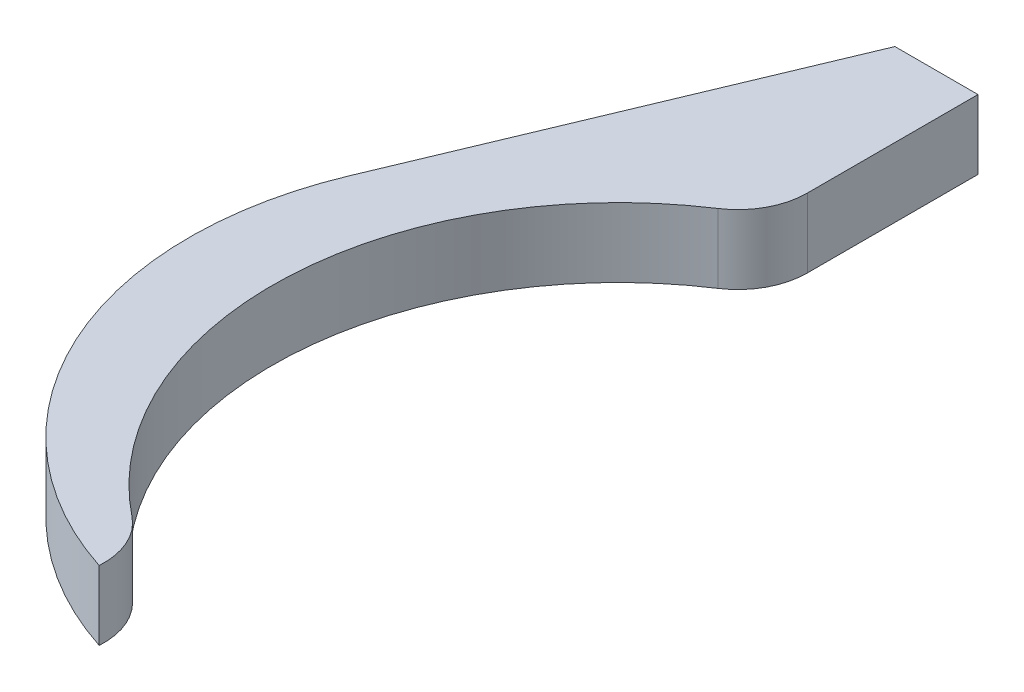
SolidWorks part; units mm, degrees
ref_plane "前视基准面" through (0, 0, 0) normal (0, 0, 1) x (1, 0, 0)
ref_plane "上视基准面" through (0, 0, 0) normal (0, 1, 0) x (1, 0, 0)
ref_plane "右视基准面" through (0, 0, 0) normal (1, 0, 0) x (0, 0, -1)
other "Configuration Table"
sketch "草图3" plane through (0, 0, 0) normal (0, 1, 0) x (1, 0, 0)
  line L0 (0, 0) -> (0, -9.9636) construction
  line L1 (-3, -3.3541) -> (3, -3.3541) construction
  line L2 (-3, -3.3541) -> (-3, -7.4162)
  line L3 (3, -3.3541) -> (3, -7.4162)
  line L7 (3, -7.4162) -> (3, -10.583)
  line L10 (-3, -43.8541) -> (3, -43.8541)
  line L11 (3, -43.8541) -> (3, -10.583)
  line L13 (-3, -7.4162) -> (-3, -43.8541)
  arc A0 (3, -3.3541) -> (-3, -3.3541) centre (0, 0) ccw
  point P6 (0, -3.3541)
  dimension "D1" = 9
  dimension "D2" = 6
  dimension "16.66" = 40.5
extrude "凸台-拉伸2" add sketch "草图3" along normal blind 5
sketch "草图4" plane through (0, 5, 0) normal (0, 1, 0) x (1, 0, 0)
  circle A0 centre (0, 0) radius 1.65
  dimension "D1" = 3.3
extrude "切除-拉伸1" cut sketch "草图4" against normal up to surface (5 mm away) up to face at (0, 0, 21.6406)
sketch "草图6" plane through (0, 5, 0) normal (0, 1, 0) x (1, 0, 0)
  line L0 (14.4495, -55.9701) -> (14.4495, -20.0301) construction
  line L1 (14.4495, -55.9701) -> (3, -43.8541) construction
  line L2 (3, -68.0861) -> (0.6636, -72.1328) construction
  line L3 (3, -43.8541) -> (-3, -43.8541) construction
  line L4 (3, -43.8541) -> (3, -33.746) construction
  line L5 (3, -43.8541) -> (3, -3.3541) construction
  line L6 (3, -33.746) -> (-3, -33.746)
  line L7 (-3, -3.3541) -> (-3, -43.8541) construction
  line L8 (14.4495, -55.9701) -> (1.9495, -77.6207) construction
  line L9 (1.9495, -77.6207) -> (0.7225, -79.746)
  arc A0 (3, -43.8541) -> (3, -68.0861) centre (14.4495, -55.9701) ccw construction
  arc A1 (-3, -43.8541) -> (0.6636, -72.1328) centre (14.4495, -55.9701) ccw construction
  arc A4 (3, -33.746) -> (1.9495, -77.6207) centre (14.4495, -55.9701) ccw
  arc A5 (-3, -33.746) -> (0.7225, -79.746) centre (8.4495, -55.9701) ccw
  dimension "D1" = 33.34
  dimension "D3" = 30
  dimension "D4" = 30
  dimension "D2" = 43.38
extrude "凸台-拉伸3" add sketch "草图6" against normal blind 5
sketch "草图7" plane through (0, 5, 0) normal (0, 1, 0) x (1, 0, 0)
  circle A0 centre (0, 0) radius 3
  dimension "D1" = 6
extrude "切除-拉伸2" cut sketch "草图7" against normal blind 3 from offset 4.5 offset against normal yes
sketch "草图8" plane through (0, 5, 0) normal (0, 1, 0) x (1, 0, 0)
  line L0 (-3, -38.0672) -> (-3, -43.8541)
  line L1 (-3, -43.8541) -> (3, -43.8541)
  line L2 (3, -43.8541) -> (3, -33.746)
  line L3 (3, -43.8541) -> (3, -3.3541) construction
  arc A0 (3, -33.746) -> (-3, -38.0672) centre (14.4495, -55.9701) ccw
extrude "切除-拉伸3" cut sketch "草图8" against normal blind 7.5
sketch "草图9" plane through (0, 5, 0) normal (0, 1, 0) x (1, 0, 0)
  line L0 (-3, -18.5501) -> (-14.615, -46.3249)
  line L1 (-3, -3.3541) -> (-3, -33.746) construction
  line L2 (-3, -18.5501) -> (-3, -33.746)
  arc A0 (-3, -33.746) -> (0.7225, -79.746) centre (8.4495, -55.9701) ccw construction
  arc A1 (-3, -33.746) -> (-14.615, -46.3249) centre (8.4495, -55.9701) ccw
extrude "凸台-拉伸4" add sketch "草图9" against normal blind 5
fillet "圆角1" radius 5 1 edges at (3, 2.5, 33.746)
fillet "圆角2" radius 5 1 edges at (1.9495, 2.5, 77.6207)
sketch "草图10" plane through (0, 5, 0) normal (0, 1, 0) x (1, 0, 0)
  line L0 (-3, -18.5501) -> (3, -18.5501)
  line L3 (3, -30.882) -> (3, -3.3541)
  line L4 (-3, -3.3541) -> (-3, -18.5501)
  line L5 (-3, -18.5501) -> (-14.615, -46.3249)
  line L6 (3, -18.5501) -> (3, -3.3541)
  line L7 (-3, -3.3541) -> (-3, -18.5501)
  arc A5 (-14.615, -46.3249) -> (0.7225, -79.746) centre (8.4495, -55.9701) ccw
  arc A6 (0.7225, -79.746) -> (-1.1472, -75.5083) centre (-4.2666, -79.4159) ccw
  arc A7 (0.7416, -35.0633) -> (-1.1472, -75.5083) centre (14.4495, -55.9701) ccw
  arc A8 (0.7416, -35.0633) -> (3, -30.882) centre (-2, -30.882) ccw
  arc A9 (3, -3.3541) -> (-3, -3.3541) centre (0, 0) ccw
  arc A14 (3, -3.3541) -> (-3, -3.3541) centre (0, 0) ccw
  dimension "D1" = 0
extrude "切除-拉伸5" cut sketch "草图10" against normal blind 5
